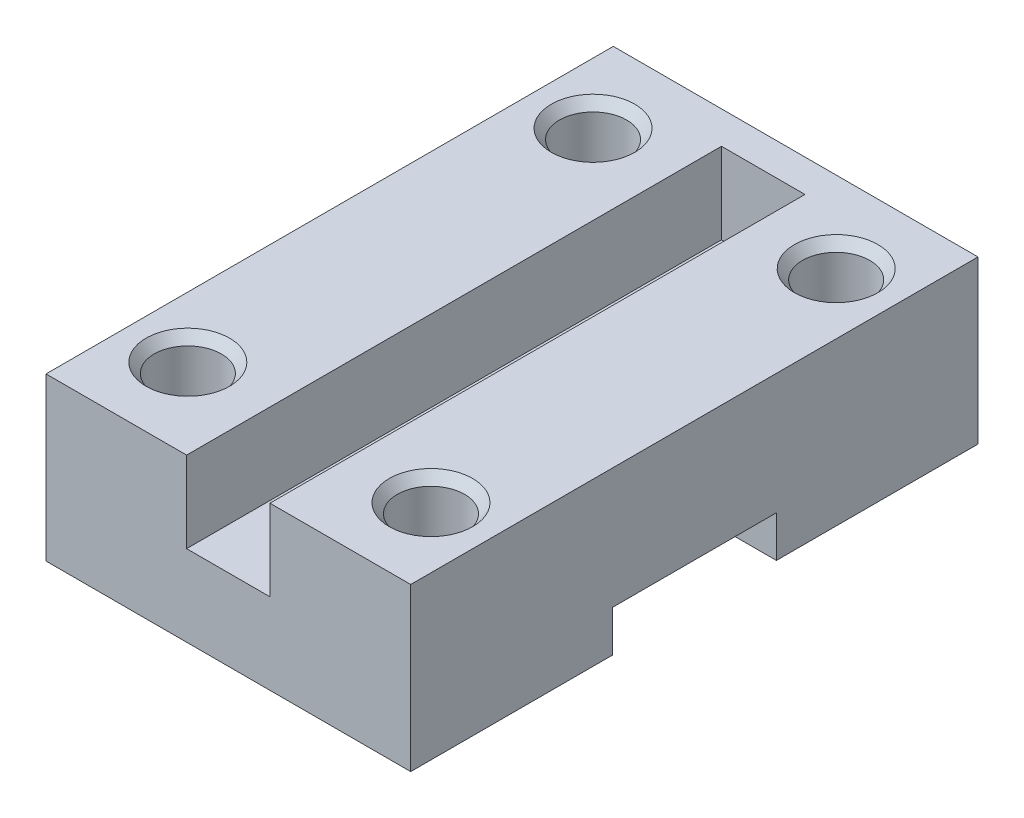
SolidWorks part; units mm, degrees
ref_plane "Спереди" through (0, 0, 0) normal (0, 0, 1) x (1, 0, 0)
ref_plane "Сверху" through (0, 0, 0) normal (0, 1, 0) x (1, 0, 0)
ref_plane "Справа" through (0, 0, 0) normal (1, 0, 0) x (0, 0, -1)
sketch "Sketch1" plane through (0, 0, 0) normal (0, 1, 0) x (1, 0, 0)
  line L1 (22.5, -35) -> (-22.5, -35)
  line L2 (22.5, -35) -> (22.5, 35)
  line L3 (22.5, 35) -> (-22.5, 35)
  line L4 (-22.5, -35) -> (-22.5, 35)
  line L5 (22.5, -35) -> (-22.5, 35) construction
  line L6 (22.5, 35) -> (-22.5, -35) construction
  point P0 (0, 0)
  dimension "D1" = 45
  dimension "D2" = 70
extrude "Boss-Extrude1" add sketch "Sketch1" along normal blind 10
sketch "Sketch2" plane through (22.5, 0, 0) normal (1, 0, 0) x (0, 0, -1)
  line L0 (0, 0) -> (0, 10) construction
  line L1 (-35, 0) -> (35, 0) construction
  line L2 (-35, 10) -> (35, 10) construction
  line L4 (10.125, 5.1) -> (-10.125, 5.1)
  line L5 (10.125, 5.1) -> (10.125, 0)
  line L6 (10.125, 0) -> (-10.125, 0)
  line L7 (-10.125, 5.1) -> (-10.125, 0)
  line L8 (10.125, 5.1) -> (-10.125, 0) construction
  line L9 (10.125, 0) -> (-10.125, 5.1) construction
  point P6 (0, 2.55)
  dimension "D1" = 20.25
  dimension "D2" = 5.1
extrude "Cut-Extrude1" cut sketch "Sketch2" against normal through all and the other way through all
sketch "Sketch3" plane through (0, 0, 0) normal (0, -1, 0) x (1, 0, 0)
  line L0 (15, -25) -> (15, 25) construction
  line L1 (-15, 25) -> (-15, -25) construction
  line L2 (-15, -25) -> (15, 25) construction
  line L3 (-22.5, -25) -> (22.5, -25) construction
  line L4 (-22.5, -35) -> (-22.5, -10.125) construction
  line L5 (22.5, -10.125) -> (22.5, -35) construction
  line L6 (-22.5, 25) -> (22.5, 25) construction
  line L7 (-22.5, 10.125) -> (-22.5, 35) construction
  line L8 (22.5, 35) -> (22.5, 10.125) construction
  line L9 (-15, 25) -> (15, -25) construction
  circle A0 centre (15, 25) radius 4.15
  circle A1 centre (15, -25) radius 4.15
  circle A2 centre (-15, -25) radius 4.15
  circle A3 centre (-15, 25) radius 4.15
  point P4 (0, 0)
  dimension "D1" = 8.3
  dimension "D2" = 30
  dimension "D3" = 50
extrude "Cut-Extrude2" cut sketch "Sketch3" against normal through all
sketch "Sketch5" plane through (0, 10, 0) normal (0, 1, 0) x (1, 0, 0)
  line L0 (5.15, 35) -> (-5.15, -35) construction
  line L1 (-5.15, -35) -> (-22.5, -35)
  line L2 (-5.15, -35) -> (-5.15, 35) construction
  line L3 (-5.15, 35) -> (-22.5, 35) construction
  line L4 (-22.5, -35) -> (-22.5, 35)
  line L5 (-5.15, -35) -> (-22.5, 35) construction
  line L6 (-5.15, 35) -> (-22.5, -35) construction
  line L7 (5.15, -35) -> (22.5, -35)
  line L8 (5.15, -35) -> (5.15, 35) construction
  line L9 (5.15, 35) -> (22.5, 35) construction
  line L10 (22.5, -35) -> (22.5, 35)
  line L11 (5.15, -35) -> (22.5, 35) construction
  line L12 (5.15, 35) -> (22.5, -35) construction
  line L13 (5.15, -35) -> (-5.15, 35) construction
  line L14 (-5.15, -35) -> (-5.15, 31)
  line L15 (-5.15, 31) -> (5.15, 31)
  line L16 (5.15, 31) -> (5.1302, -34.9493)
  line L17 (5.15, -35) -> (5.1302, -34.9493)
  line L18 (-22.5, 35) -> (22.5, 35)
  circle A0 centre (-15, 25) radius 4.15
  circle A1 centre (15, 25) radius 4.15
  circle A2 centre (15, -25) radius 4.15
  circle A3 centre (-15, -25) radius 4.15
  point P0 (-13.825, 0)
  point P6 (13.825, 0)
  point P12 (0, 0)
  dimension "D1" = 10.3
  dimension "D2" = 4
extrude "Boss-Extrude2" add sketch "Sketch5" along normal blind 10
chamfer "Chamfer1" distance 1 angle 50 4 edges at (15, 20, 29.15) (-15, 20, 29.15) (-15, 20, -20.85) (15, 20, -20.85) first distance on face at (15, 20, 29.15)
